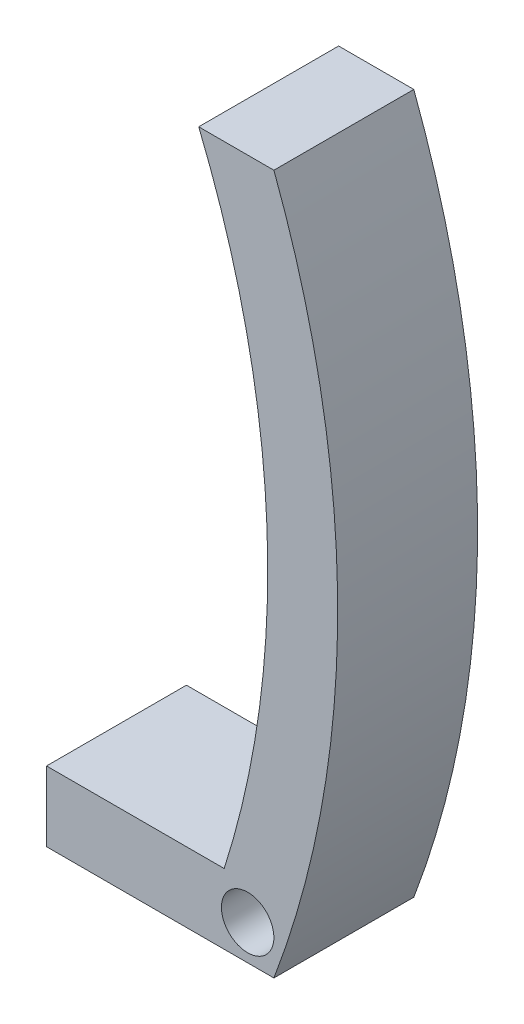
SolidWorks part; units mm, degrees
ref_plane "Front" through (0, 0, 0) normal (0, 0, 1) x (1, 0, 0)
ref_plane "Top" through (0, 0, 0) normal (0, 1, 0) x (1, 0, 0)
ref_plane "Right" through (0, 0, 0) normal (1, 0, 0) x (0, 0, -1)
sketch "Sketch1" plane through (0, 0, 0) normal (0, 0, 1) x (1, 0, 0)
  line L0 (0, 0) -> (16.51, 0)
  line L1 (0, 0) -> (0, 5.08)
  line L2 (0, 5.08) -> (12.9005, 5.08)
  line L3 (16.51, 50.8) -> (11.0506, 50.8)
  arc A0 (16.51, 0) -> (16.51, 50.8) centre (-50.8, 25.4) ccw
  arc A1 (12.9005, 5.08) -> (11.0506, 50.8) centre (-50.8, 25.4) ccw
  point P3 (0, 0)
  dimension "D1" = 16.51
  dimension "D2" = 50.8
  dimension "D5" = 5.08
  dimension "D3" = 5.08
  dimension "D4" = 50.8
extrude "Boss-Extrude1" add sketch "Sketch1" along normal blind 10.16
sketch "Sketch2" plane through (0, 0, 10.16) normal (0, 0, 1) x (1, 0, 0)
  line L0 (0, 5.08) -> (0, 0) construction
  circle A0 centre (14.605, 2.54) radius 1.905
  point P2 (0, 2.54)
  point P3 (0, 0)
  dimension "D1" = 3.81
  dimension "D2" = 14.605
extrude "Cut-Extrude1" cut sketch "Sketch2" against normal through all and the other way through all
